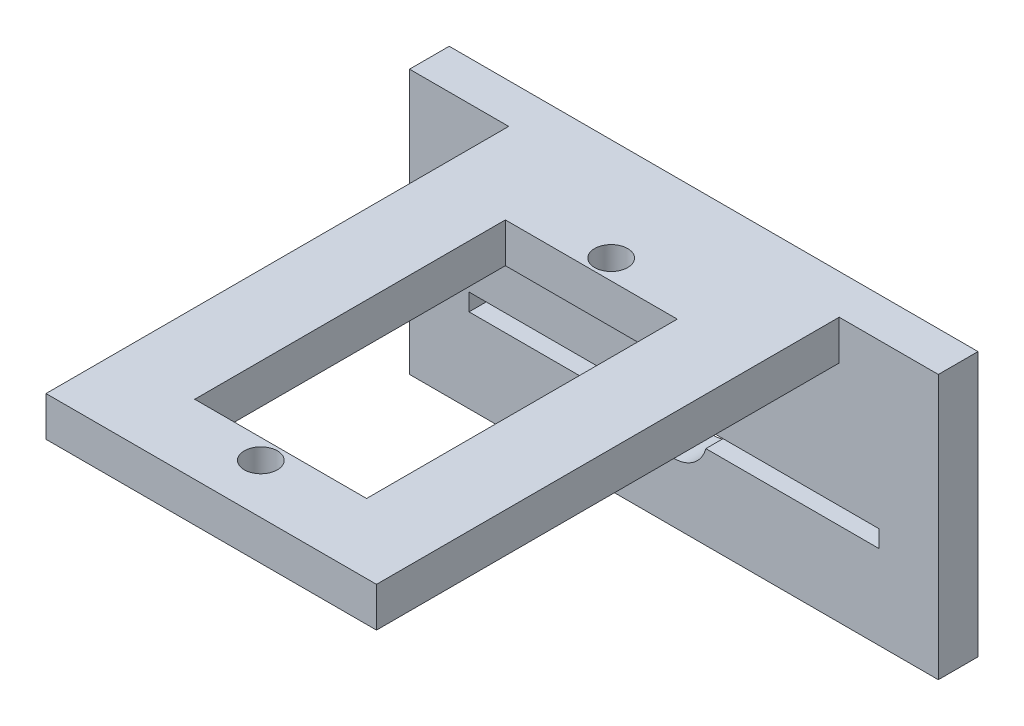
SolidWorks part; units mm, degrees
ref_plane "Plano frontal" through (0, 0, 0) normal (0, 0, 1) x (1, 0, 0)
ref_plane "Plano superior" through (0, 0, 0) normal (0, 1, 0) x (1, 0, 0)
ref_plane "Plano direito" through (0, 0, 0) normal (1, 0, 0) x (0, 0, -1)
sketch "Esboço1" plane through (0, 0, 0) normal (0, 0, 1) x (1, 0, 0)
  line L13 (-20, -12) -> (20, -12)
  line L14 (-20, -12) -> (-20, 8)
  line L15 (-20, 8) -> (20, 8)
  line L16 (20, -12) -> (20, 8)
  arc A12 (-2.4269, 0.6) -> (-2.4269, -0.6) centre (0, 0) ccw
  point P0 (0, 0)
  point P29 (0, 8)
  dimension "D8" = 5
  dimension "D3" = 20
  dimension "D4" = 40
  dimension "D5" = 12
extrude "Ressalto-extrusão1" add sketch "Esboço1" against normal blind 1 contours L13 L16 L15 L14 region at (0, -2, 0)
sketch "Esboço2" plane through (0, 0, 0) normal (0, 0, 1) x (1, 0, 0)
  line L0 (0, -5) -> (0, 8) construction
  line L1 (-20, 8) -> (20, 8) construction
  line L2 (-2.414, -4.35) -> (-15.5, -4.35)
  line L3 (15.5, -4.35) -> (2.414, -4.35)
  line L4 (15.5, -4.35) -> (15.5, -5.65)
  line L5 (15.5, -5.65) -> (2.414, -5.65)
  line L6 (-15.5, -4.35) -> (-15.5, -5.65)
  line L7 (15.5, -4.35) -> (-15.5, -5.65) construction
  line L8 (15.5, -5.65) -> (-15.5, -4.35) construction
  line L9 (-2.414, -5.65) -> (-15.5, -5.65)
  arc A1 (-2.414, -5.65) -> (2.414, -5.65) centre (0, -5) ccw
  arc A17 (2.414, -4.35) -> (-2.414, -4.35) centre (0, -5) ccw
  dimension "D1" = 5
  dimension "D2" = 1.3
  dimension "D3" = 31
  dimension "D4" = 13
sketch "Esboço3" plane through (0, 0, 0) normal (0, 0, 1) x (1, 0, 0)
  line L1 (-20, -12) -> (20, -12)
  line L2 (-20, -12) -> (-20, 8)
  line L3 (-20, 8) -> (20, 8)
  line L4 (20, -12) -> (20, 8)
extrude "Ressalto-extrusão2" add sketch "Esboço3" along normal blind 2
extrude "Corte-extrusão1" cut sketch "Esboço2" along normal up to surface and the other way up to surface up to face at (0, -2, 2) other way up to face at (0, -2, -1)
sketch "Esboço4" plane through (0, 8, 0) normal (0, 1, 0) x (1, 0, 0)
  line L0 (20, -2) -> (-20, -2) construction
  line L1 (6.5, -31.75) -> (-6.5, -31.75)
  line L2 (6.5, -31.75) -> (6.5, -8.25)
  line L3 (6.5, -8.25) -> (-6.5, -8.25)
  line L4 (-6.5, -31.75) -> (-6.5, -8.25)
  line L5 (-20, 1) -> (20, 1) construction
  line L6 (12.5, -2) -> (-12.5, -2)
  line L7 (12.5, -2) -> (12.5, -37)
  line L8 (12.5, -37) -> (-12.5, -37)
  line L9 (-12.5, -2) -> (-12.5, -37)
  line L10 (-12.5, -2) -> (12.5, -2)
  line L11 (-12.5, -2) -> (-12.5, 1)
  line L12 (-12.5, 1) -> (12.5, 1)
  line L13 (12.5, -2) -> (12.5, 1)
  circle A0 centre (0, -6.75) radius 1.25
  circle A1 centre (0, -33.25) radius 1.25
  point P6 (0, -31.75)
  point P13 (0, -2)
  point P14 (0, -37)
  line M5 (-20, -2) -> (20, -2)
  line M7 (20, 1) -> (-20, 1)
  dimension "D6" = 4.75
  dimension "D7" = 2.5
  dimension "D8" = 26.5
  dimension "D1" = 6.25
  dimension "D2" = 23.5
  dimension "D3" = 13
  dimension "D4" = 25
  dimension "D5" = 35
extrude "Ressalto-extrusão3" add sketch "Esboço4" against normal blind 3 contours L13 L11 M5 M7 | L9 L8 L7 L1 L4 L3 L2 M5 region at (12.0699, 8, 19.5) region at (0, 8, 0.5)
